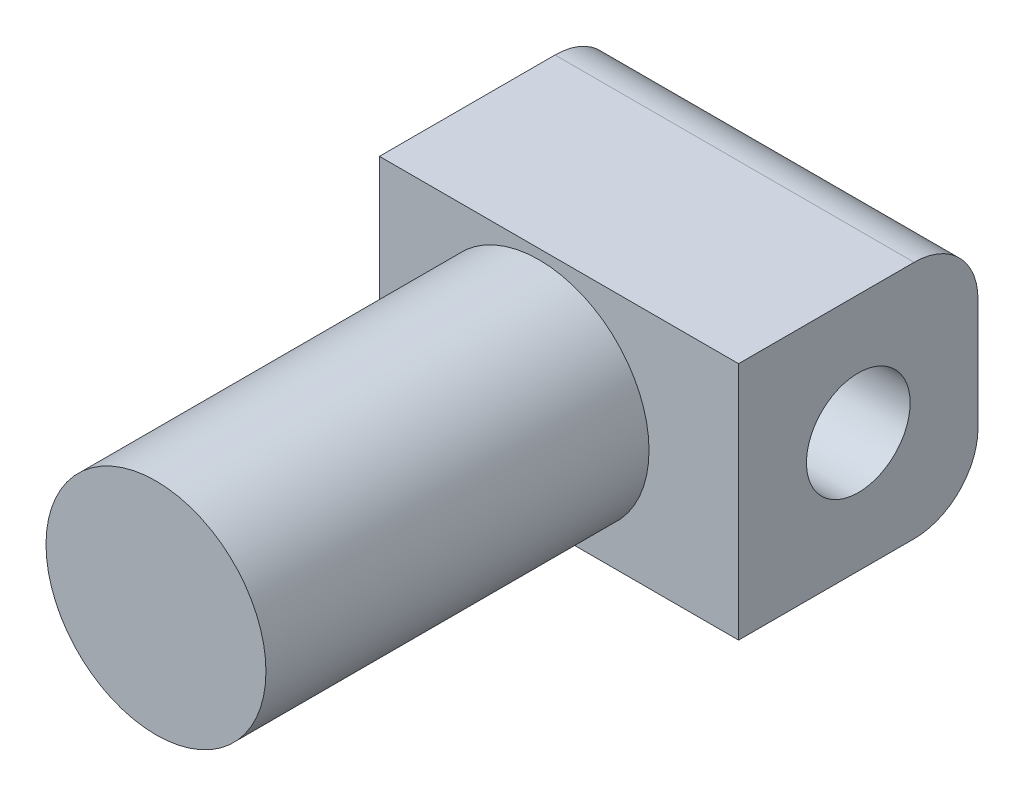
SolidWorks part; units mm, degrees
material "6061-T6 (SS)"
ref_plane "Front Plane" through (0, 0, 0) normal (1, 0, 0) x (0, 1, 0)
ref_plane "Top Plane" through (0, 0, 0) normal (0, 0, 1) x (0, 1, 0)
ref_plane "Right Plane" through (0, 0, 0) normal (0, 1, 0) x (-1, 0, 0)
sketch "Sketch1" plane through (0, 0, 0) normal (0, 0, 1) x (0, 1, 0)
  line L1 (0, 0) -> (-7.62, 0)
  line L2 (0, 0) -> (0, 11.43)
  line L3 (0, 11.43) -> (-7.62, 11.43)
  line L4 (-7.62, 0) -> (-7.62, 11.43)
  dimension "D1" = 7.62
  dimension "D2" = 11.43
extrude "Boss-Extrude1" add sketch "Sketch1" along normal blind 7.62
sketch "Sketch2" plane through (0, 0, 7.62) normal (0, 0, 1) x (1, 0, 0)
  line L0 (-11.43, -3.81) -> (0, -3.81) construction
  line L1 (-11.43, 0) -> (-11.43, -7.62) construction
  line L2 (0, -7.62) -> (0, 0) construction
  circle A0 centre (-6.35, -3.81) radius 3.5
  point P6 (-6.35, -3.81)
  dimension "D2" = 7
  dimension "D1" = 5.08
extrude "Boss-Extrude2" add sketch "Sketch2" along normal blind 12.192
sketch "Sketch3" plane through (0, 0, 0) normal (1, 0, 0) x (0, 1, 0)
  line L0 (-7.62, 7.62) -> (0, 0) construction
  line L1 (0, 7.62) -> (-7.62, 0) construction
hole_wizard "Tap Drill for M4x0.7 Tap1" positions "Sketch4" profile "Sketch5" hole size "M4x0.7" standard "ANSI Metric" end condition through all
sketch "Sketch4" plane through (0, 0, 0) normal (1, 0, 0) x (0, 0, -1)
  line L0 (-7.62, -7.62) -> (0, 0) construction
  point P0 (-3.81, -3.81)
sketch "Sketch5" plane through (0, -3.81, 3.81) normal (0, 1, 0) x (0, 0, -1)
  line L0 (0, 0) -> (0, 11.43)
  line L1 (0, 11.43) -> (1.65, 11.43)
  line L2 (1.65, 11.43) -> (1.65, 0)
  line L5 (1.65, 0) -> (0, 0)
  line L11 (0, -6.35) -> (0, 107.95) construction
  dimension "Thru Hole Dia." = 3.3
  dimension "Thru Hole Depth" = 11.43
fillet "Fillet1" radius 2.032 2 edges at (-5.715, 0, 0) (-5.715, -7.62, 0)
equation "\"D2@Sketch2\"=7mm"
